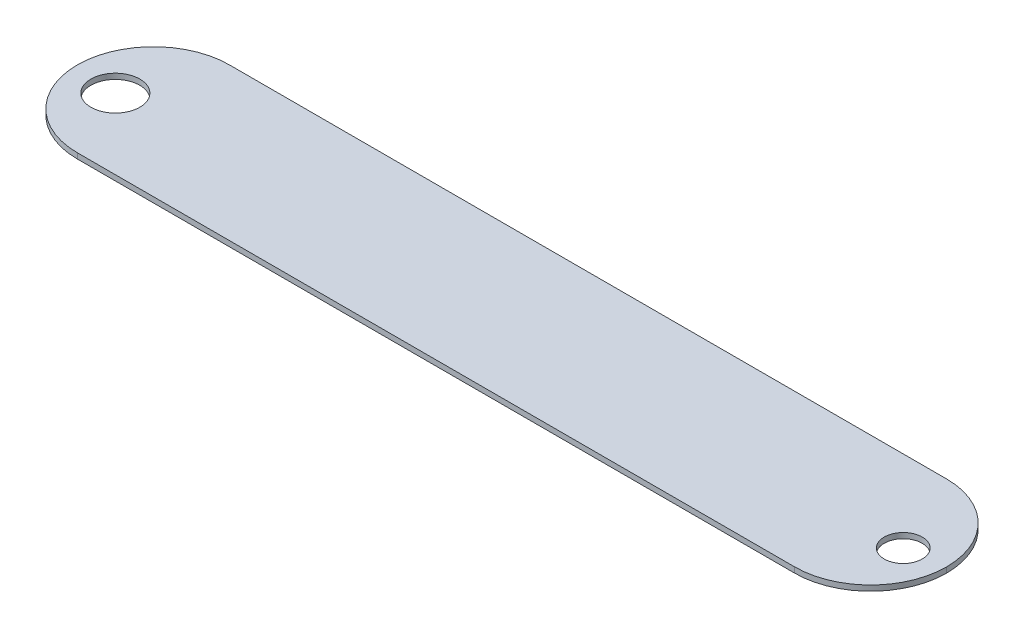
SolidWorks part; units mm, degrees
ref_plane "前视基准面" through (0, 0, 0) normal (0, 0, 1) x (1, 0, 0)
ref_plane "上视基准面" through (0, 0, 0) normal (0, 1, 0) x (1, 0, 0)
ref_plane "右视基准面" through (0, 0, 0) normal (1, 0, 0) x (0, 0, -1)
other "Configuration Table"
sketch "草图1" plane through (0, 0, 0) normal (0, 1, 0) x (1, 0, 0)
  line L0 (-10.2491, -7.5) -> (85.1528, -7.5) construction
  line L1 (0, 0) -> (80, 0)
  line L2 (0, 0) -> (0, -14)
  line L3 (0, -14) -> (80, -14)
  line L4 (80, 0) -> (80, -14)
  circle A0 centre (4, -7.5) radius 2.25
  circle A1 centre (76.5, -7.5) radius 1.75
  dimension "D3" = 4.5
  dimension "D4" = 3.5
  dimension "D1" = 80
  dimension "D2" = 14
  dimension "D5" = 4
  dimension "D6" = 3.5
extrude "凸台-拉伸1" add sketch "草图1" along normal blind 0.5
fillet "圆角1" radius 7 4 edges at (0, 0.25, 0) (80, 0.25, 0) (80, 0.25, 14) (0, 0.25, 14)
